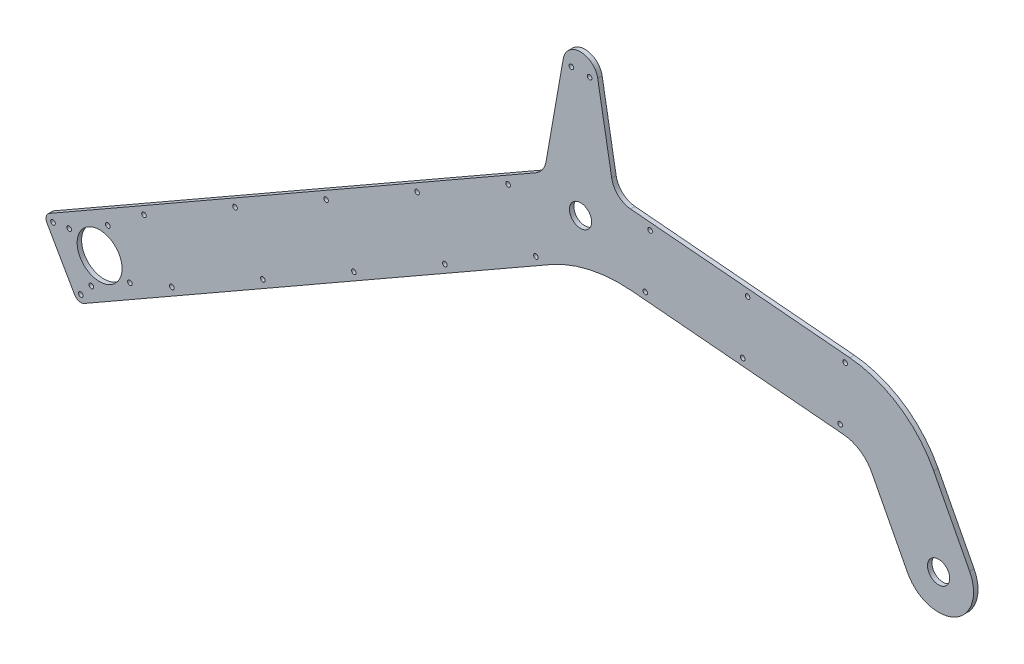
SolidWorks part; units mm, degrees
material "6061-T6 (SS)"
ref_plane "Front Plane" through (0, 0, 0) normal (0, 0, 1) x (1, 0, 0)
ref_plane "Top Plane" through (0, 0, 0) normal (0, 1, 0) x (1, 0, 0)
ref_plane "Right Plane" through (0, 0, 0) normal (1, 0, 0) x (0, 0, -1)
sketch "Reference Sketch" plane through (0, 0, 0) normal (0, 0, 1) x (1, 0, 0)
  line L0 (-343.92, -196.825) -> (0, 0) construction
  line L1 (-243.92, 103.175) -> (356.08, 103.175) construction
  line L2 (-243.92, 103.175) -> (-243.92, 0) construction
  line L3 (-243.92, 0) -> (356.08, 0) construction
  line L4 (356.08, 103.175) -> (356.08, 0) construction
  line L5 (0, 0) -> (256.08, -92.7116) construction
  line L6 (256.08, -92.7116) -> (56.08, -196.825) construction
  line L7 (256.08, -92.7116) -> (456.08, -196.825) construction
  line L8 (-343.92, -196.825) -> (56.08, -196.825) construction
  line L9 (56.08, -196.825) -> (456.08, -196.825) construction
  circle A1 centre (-343.92, -196.825) radius 100 construction
  circle A2 centre (56.08, -196.825) radius 100 construction
  circle A3 centre (456.08, -196.825) radius 100 construction
  circle A4 centre (-343.92, -196.825) radius 16.05 construction
  circle A5 centre (-343.92, -196.825) radius 28.55 construction
  circle A6 centre (-343.92, -196.825) radius 38.55 construction
  circle A7 centre (-343.92, -196.825) radius 33.55 construction
  point P13 (-343.92, -296.825)
  point P14 (556.08, -196.825)
  point P17 (-443.92, -196.825)
  dimension "D3" = 32.1
  dimension "D5" = 200
  dimension "D9" = 57.1
  dimension "D10" = 10
  dimension "D11" = 5
  dimension "D1" = 600
  dimension "D2" = 103.175
  dimension "D4" = 243.92
  dimension "D6" = 125
  dimension "D7" = 400
  dimension "D8" = 1000
sketch "Sketch2" plane through (0, 0, 0) normal (0, 0, 1) x (1, 0, 0)
  line L0 (-379.7168, -188.5069) -> (-32.0065, 10.4873)
  line L1 (-354.8814, -231.9028) -> (-21.5627, -41.1449)
  line L2 (-343.92, -196.825) -> (0, 0) construction
  line L3 (-184.3777, -76.7146) -> (-159.5423, -120.1104) construction
  line L4 (-24.685, 20.9013) -> (-12.3101, 91.0831)
  line L5 (12.3101, 91.0831) -> (22.322, 34.3028)
  line L6 (0, 98.4125) -> (0, 112.7) construction
  line L7 (-5.4848, 79.4125) -> (5.4848, 79.4125) construction
  line L8 (5.4848, 79.4125) -> (10.9697, 88.9125) construction
  line L9 (10.9697, 88.9125) -> (5.4848, 98.4125) construction
  line L10 (5.4848, 98.4125) -> (-5.4848, 98.4125) construction
  line L11 (-5.4848, 98.4125) -> (-10.9697, 88.9125) construction
  line L12 (-10.9697, 88.9125) -> (-5.4848, 79.4125) construction
  line L13 (-243.92, 103.175) -> (356.08, 103.175) construction
  line L14 (0, 88.9125) -> (0, 0) construction
  line L15 (35.7868, 21.9646) -> (192.5861, 8.2464)
  line L16 (252.5753, -31.8371) -> (278.2553, -81.1679)
  line L17 (233.9047, -104.2553) -> (208.2247, -54.9245)
  line L18 (36.8237, -28.3172) -> (188.2284, -41.5633)
  line L19 (0, 0) -> (192.5861, -16.8491) construction
  line L21 (-365.6311, -190.9191) -> (-338.0141, -175.1139) construction
  line L22 (-381.5729, -195.33) -> (-361.7045, -230.0467)
  line L23 (256.08, -92.7116) -> (56.08, -196.825) construction
  line L25 (-243.92, 0) -> (356.08, 0) construction
  circle A0 centre (0, 0) radius 7.9375
  circle A1 centre (-343.92, -196.825) radius 16.05
  arc A3 (-12.3101, 91.0831) -> (12.3101, 91.0831) centre (0, 88.9125) cw
  circle A4 centre (0, 88.9125) radius 6.5 construction
  circle A5 centre (-6.5, 88.9125) radius 1.65
  circle A6 centre (6.5, 88.9125) radius 1.65
  circle A7 centre (0, 88.9125) radius 9.5 construction
  arc A8 (252.5753, -31.8371) -> (192.5861, 8.2464) centre (186.0495, -66.4682) ccw
  circle A9 centre (256.08, -92.7116) radius 7.9375
  arc A10 (278.2553, -81.1679) -> (233.9047, -104.2553) centre (256.08, -92.7116) cw
  arc A11 (-21.5627, -41.1449) -> (36.8237, -28.3172) centre (28.1082, -127.9366) cw
  arc A12 (188.2284, -41.5633) -> (208.2247, -54.9245) centre (186.0495, -66.4682) cw
  arc A13 (22.322, 34.3028) -> (35.7868, 21.9646) centre (37.0941, 36.9075) ccw
  arc A14 (-32.0065, 10.4873) -> (-24.685, 20.9013) centre (-39.4572, 23.506) ccw
  circle A17 centre (-343.92, -196.825) radius 22.5 construction
  circle A18 centre (-365.6311, -190.9191) radius 1.65
  circle A19 centre (-338.0141, -175.1139) radius 1.65
  circle A20 centre (-322.2089, -202.7309) radius 1.65
  circle A21 centre (-349.8259, -218.5361) radius 1.65
  arc A27 (-379.7168, -188.5069) -> (-381.5729, -195.33) centre (-377.2333, -192.8465) ccw
  arc A28 (-361.7045, -230.0467) -> (-354.8814, -231.9028) centre (-357.3649, -227.5632) ccw
  circle A29 centre (-343.92, -196.825) radius 33.55 construction
  circle A32 centre (-343.92, -196.825) radius 38.55 construction
  point P16 (-171.96, -98.4125)
  point P64 (-343.92, -196.825)
  dimension "D1" = 15.875
  dimension "D2" = 32.1
  dimension "D3" = 45
  dimension "D5" = 13
  dimension "D6" = 3.3
  dimension "D7" = 6
  dimension "D12" = 50
  dimension "D14" = 100
  dimension "D16" = 15
  dimension "D17" = 5
  dimension "D18" = 25
  dimension "D19" = 3.3
  dimension "D15" = 4
  dimension "D4" = 50
  dimension "D8" = 19
  dimension "D9" = 14.2875
  dimension "D10" = 9.525
  dimension "D11" = 10
  dimension "D13" = 50
extrude "Base" add sketch "Sketch2" along normal blind 3.175
sketch "Sketch3" plane through (0, 0, 3.175) normal (0, 0, 1) x (1, 0, 0)
  line L0 (-343.92, -196.825) -> (0, 0) construction
  line L5 (0, 0) -> (197.3986, -17.2701) construction
  line L6 (192.5861, 8.2464) -> (35.7868, 21.9646) construction
  line L9 (36.8237, -28.3172) -> (188.2284, -41.5633) construction
  line L10 (-31.8958, -41.2976) -> (0, 0) construction
  line L11 (0, 0) -> (46.2693, -24.1244) construction
  circle A0 centre (-357.3649, -227.5632) radius 1.65
  circle A1 centre (-343.92, -196.825) radius 33.55 construction
  arc A2 (-361.7045, -230.0467) -> (-354.8814, -231.9028) centre (-357.3649, -227.5632) ccw construction
  circle A3 centre (-292.2711, -190.3101) radius 1.65
  circle A4 centre (-227.1773, -153.057) radius 1.65
  circle A5 centre (-162.0835, -115.8038) radius 1.65
  circle A6 centre (-96.9897, -78.5507) radius 1.65
  circle A7 centre (-31.8958, -41.2976) radius 1.65
  circle A8 centre (-312.1394, -155.5934) radius 1.65
  circle A9 centre (-377.2333, -192.8465) radius 1.65
  circle A10 centre (-247.0456, -118.3403) radius 1.65
  circle A11 centre (-181.9518, -81.0871) radius 1.65
  circle A12 centre (-116.858, -43.834) radius 1.65
  circle A13 centre (-51.7642, -6.5809) radius 1.65
  circle A14 centre (46.2693, -24.1244) radius 1.65
  circle A15 centre (116.0029, -30.2253) radius 1.65
  circle A16 centre (185.7366, -36.3262) radius 1.65
  circle A17 centre (189.2228, 3.5215) radius 1.65
  circle A18 centre (119.4892, 9.6224) radius 1.65
  circle A19 centre (49.7555, 15.7234) radius 1.65
  dimension "D1" = 3.3
  dimension "D2" = 6
  dimension "D3" = 5
  dimension "D5" = 3
  dimension "D4" = 75
  dimension "D6" = 70
extrude "Strut Holes" cut sketch "Sketch3" against normal through all
